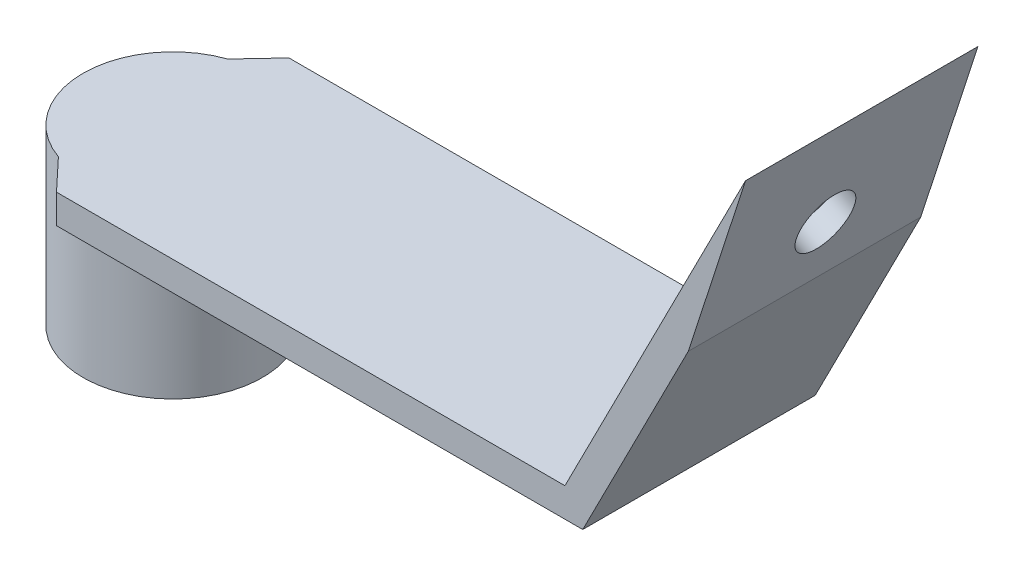
SolidWorks part; units mm, degrees
ref_plane "Front" through (0, 0, 0) normal (0, 0, 1) x (1, 0, 0)
ref_plane "Top" through (0, 0, 0) normal (0, 1, 0) x (1, 0, 0)
ref_plane "Right" through (0, 0, 0) normal (1, 0, 0) x (0, 0, -1)
sketch "Sketch1" plane through (0, 0, 0) normal (0, 0, 1) x (1, 0, 0)
  line L0 (-76.4958, -3.4222) -> (-20.9415, -3.4222)
  line L1 (-20.9415, -3.4222) -> (-1.2089, 35.3052)
  line L3 (-76.4958, -6.5972) -> (-18.9958, -6.5972)
  line L6 (-76.4958, -3.4222) -> (-76.4958, -6.5972)
  line L8 (-7.4645, 16.0344) -> (-1.2089, 35.3052)
  line L9 (-1.2089, 35.3052) -> (23.8053, 30.1317) construction
  line L10 (0.5203, 31.7054) -> (23.1623, 27.0225) construction
  line L11 (-18.9958, -6.5972) -> (-7.4645, 16.0344)
  line L12 (-18.9958, -6.5972) -> (0.5203, 31.7054) construction
  dimension "D2" = 57.5
  dimension "D3" = 25.4
  dimension "D4" = 117
  dimension "D1" = 3.175
extrude "Boss-Extrude1" add sketch "Sketch1" along normal blind 25.4
sketch "Sketch2" plane through (0, -3.4222, 0) normal (0, 1, 0) x (1, 0, 0)
  line L0 (-76.4958, -25.4) -> (-76.4958, 0) construction
  circle A0 centre (-76.4958, -12.7) radius 7.0714
  circle A1 centre (-76.4958, -12.7) radius 9.8014
extrude "Boss-Extrude2" add sketch "Sketch2" against normal blind 19
sketch "Sketch3" plane through (0, -3.4222, 0) normal (0, 1, 0) x (1, 0, 0)
  line L0 (-76.4958, 0) -> (-85.9296, -10.0406)
  line L1 (-85.9296, -10.0406) -> (-85.9296, -15.3594)
  line L2 (-85.9296, -15.3594) -> (-76.4958, -25.4)
  line L3 (-76.4958, 0) -> (-76.4958, -25.4)
  line L4 (-85.9296, -10.0406) -> (-86.2973, -12.7)
  line L5 (-86.2973, -12.7) -> (-85.9296, -15.3594)
  arc A0 (-76.4958, -2.8986) -> (-76.4958, -22.5014) centre (-76.4958, -12.7) ccw construction
  line M1 (-76.4958, 0) -> (-76.4958, -2.8986)
  arc M2 (-76.4958, -2.8986) -> (-76.4958, -22.5014) centre (-76.4958, -12.7) ccw
  line M3 (-76.4958, -22.5014) -> (-76.4958, -25.4)
  arc M7 (-76.4958, -19.7714) -> (-76.4958, -5.6286) centre (-76.4958, -12.7) cw
  line M8 (-76.4958, -5.6286) -> (-76.4958, -19.7714)
extrude "Boss-Extrude3" add sketch "Sketch3" against normal blind 3.175 contours L1 M7 | L4 L5 L1 M7 | L3 L1 M7 M2 | L2 M2 M3 | L1 M7 M8 | L3 L1 M2 M7 | L0 M1 M2 region at (-77.5382, -3.4222, 2.0466) region at (-78.1034, -3.4222, 3.2519) region at (-86.0521, -3.4222, 12.7) region at (-79.497, -3.4222, 12.7) region at (-77.5382, -3.4222, 23.3534)
sketch "Sketch4" plane through (-15.241, 7.7657, 0) normal (-0.891, 0.454, 0) x (0, 0, 1)
  line L0 (25.4, 30.9084) -> (25.4, -12.5564) construction
  line L1 (25.4, 30.9084) -> (0, 30.9084) construction
  circle A0 centre (12.7, 18.2084) radius 3.175
  dimension "D1" = 6.35
  dimension "D2" = 12.7
  dimension "D3" = 12.7
extrude "Cut-Extrude1" cut sketch "Sketch4" against normal blind 3.175
